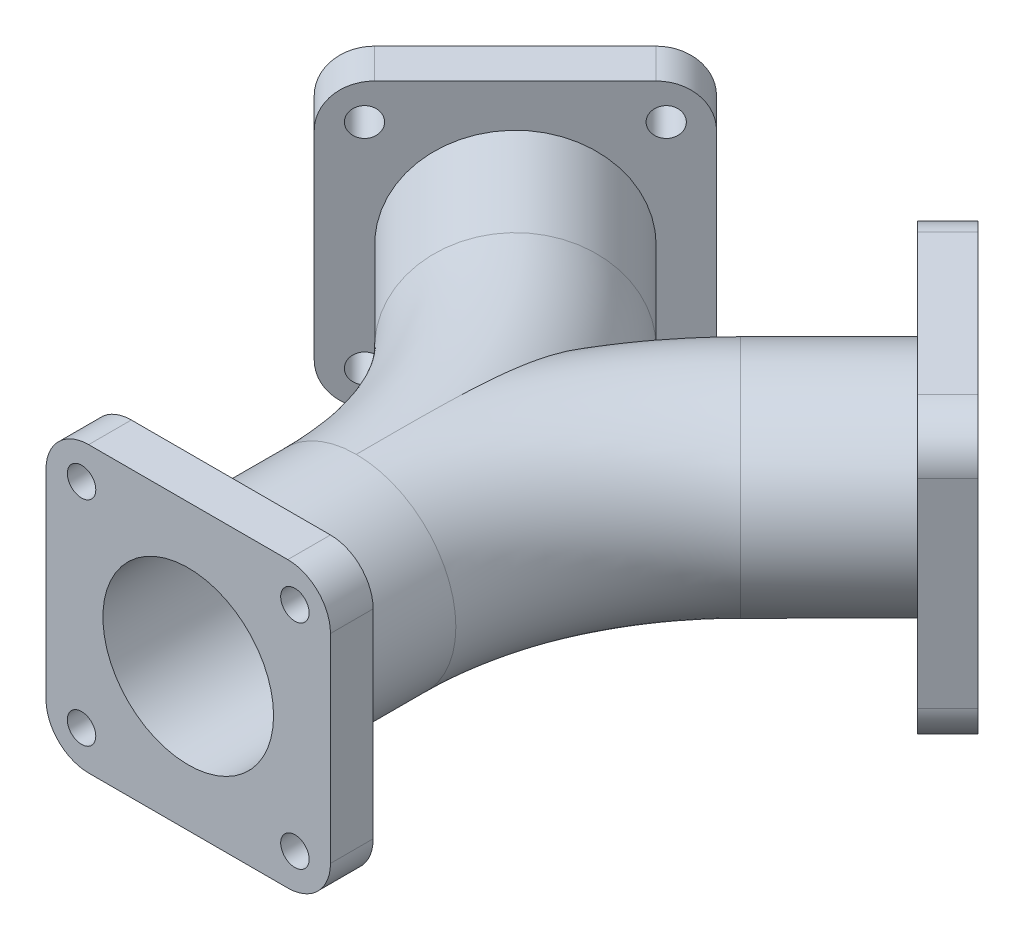
SolidWorks part; units mm, degrees
ref_plane "Alzado" through (0, 0, 0) normal (0, 0, 1) x (1, 0, 0)
ref_plane "Planta" through (0, 0, 0) normal (0, 1, 0) x (1, 0, 0)
ref_plane "Vista lateral" through (0, 0, 0) normal (1, 0, 0) x (0, 0, -1)
sketch "Croquis1" plane through (0, 0, 0) normal (0, 0, 1) x (1, 0, 0)
  line L1 (-50, -50) -> (50, -50)
  line L2 (-50, -50) -> (-50, 50)
  line L3 (-50, 50) -> (50, 50)
  line L4 (50, -50) -> (50, 50)
  line L5 (-50, -50) -> (50, 50) construction
  line L6 (-50, 50) -> (50, -50) construction
  point P0 (0, 0)
  dimension "D1" = 100
  dimension "D2" = 100
extrude "Saliente-Extruir1" add sketch "Croquis1" along normal blind 15
fillet "Redondeo1" radius 15 4 edges at (50, 50, 7.5) (-50, 50, 7.5) (-50, -50, 7.5) (50, -50, 7.5)
sketch "Croquis2" plane through (0, 0, 15) normal (0, 0, 1) x (1, 0, 0)
  circle A0 centre (0, 0) radius 30
  circle A2 centre (-37.5, -37.5) radius 5
  circle A3 centre (37.5, 37.5) radius 5
  circle A4 centre (37.5, -37.5) radius 5
  circle A5 centre (-37.5, 37.5) radius 5
extrude "Cortar-Extruir2" cut sketch "Croquis2" against normal blind 22
sketch "Croquis7" plane through (0, 0, 0) normal (0, 1, 0) x (1, 0, 0)
  line L0 (0, 0) -> (0, 44.0812)
  line L1 (39.5406, 139.5406) -> (70.7107, 170.7107)
  arc A0 (0, 44.0812) -> (39.5406, 139.5406) centre (135, 44.0812) cw
  dimension "D1" = 135
sketch "Croquis10" plane through (0, 0, 0) normal (0, 0, 1) x (1, 0, 0)
  circle A0 centre (0, 0) radius 30
  circle A1 centre (0, 0) radius 35
sweep "Barrer1" add profiles "Croquis10" path "Croquis7"
sketch "Croquis12" plane through (0, 0, 0) normal (0, 1, 0) x (1, 0, 0)
  line L0 (70.7107, 170.7107) -> (120.3144, 121.1069) construction
  line L1 (95.4594, 145.9619) -> (45.9619, 195.4594) construction
  line L2 (120.3144, 121.1069) -> (21.6981, 219.7232) construction
  line L3 (182.9938, 58.4276) -> (58.4276, 182.9938) construction
ref_plane "Plano1" through (120.7107, 0, -120.7107) normal (0.7071, 0, -0.7071) x (-0.7071, 0, -0.7071)
sketch "Croquis14" plane through (120.7107, 0, -120.7107) normal (0.7071, 0, -0.7071) x (-0.7071, 0, -0.7071)
  line L1 (20.7107, 50) -> (120.7107, 50)
  line L2 (20.7107, 50) -> (20.7107, -50)
  line L3 (20.7107, -50) -> (120.7107, -50)
  line L4 (120.7107, 50) -> (120.7107, -50)
  line L5 (20.7107, 50) -> (120.7107, -50) construction
  line L6 (20.7107, -50) -> (120.7107, 50) construction
  point P0 (70.7107, 0)
  dimension "D1" = 100
  dimension "D2" = 100
extrude "Saliente-Extruir2" add sketch "Croquis14" along normal blind 15
sketch "Croquis15" plane through (120.7107, 0, -120.7107) normal (0.7071, 0, -0.7071) x (-0.7071, 0, -0.7071)
  circle A0 centre (70.7107, 0) radius 30
  circle A1 centre (108.2107, -37.5) radius 5
  circle A2 centre (33.2107, -37.5) radius 5
  circle A3 centre (33.2107, 37.5) radius 5
  circle A4 centre (108.2107, 37.5) radius 5
extrude "Cortar-Extruir3" cut sketch "Croquis15" along normal blind 27
fillet "Redondeo2" radius 15 4 edges at (111.3693, 50, -140.6586) (111.3693, -50, -140.6586) (40.6586, 50, -211.3693) (40.6586, -50, -211.3693)
sketch "Croquis18" plane through (0, 0, 0) normal (0, 1, 0) x (1, 0, 0)
  line L0 (0, 0) -> (0, 44.0812)
  line L1 (35, 0) -> (-35, 0) construction
  line L2 (-39.5406, 139.5406) -> (-70.7107, 170.7107)
  arc A0 (0, 44.0812) -> (-39.5406, 139.5406) centre (-135, 44.0812) ccw
  dimension "D1" = 135
sketch "Croquis19" plane through (0, 0, 0) normal (0, 0, 1) x (1, 0, 0)
  circle A0 centre (0, 0) radius 30
  circle A1 centre (0, 0) radius 35
sweep "Barrer4" add profiles "Croquis19" path "Croquis18"
sketch "Croquis21" plane through (0, 0, 0) normal (0, 1, 0) x (1, 0, 0)
  line L0 (-70.7107, 170.7107) -> (-24.3051, 217.1162) construction
  line L1 (-49.4975, 191.9239) -> (-91.9239, 149.4975) construction
  line L2 (-24.3051, 217.1162) -> (-137.9274, 103.4939) construction
sketch "Croquis23" plane through (-120.7107, 0, -120.7107) normal (-0.7071, 0, -0.7071) x (-0.7071, 0, 0.7071)
  line L1 (-120.7107, -50) -> (-20.7107, -50)
  line L2 (-120.7107, -50) -> (-120.7107, 50)
  line L3 (-120.7107, 50) -> (-20.7107, 50)
  line L4 (-20.7107, -50) -> (-20.7107, 50)
  line L5 (-120.7107, -50) -> (-20.7107, 50) construction
  line L6 (-120.7107, 50) -> (-20.7107, -50) construction
  point P0 (-70.7107, 0)
  dimension "D1" = 100
extrude "Saliente-Extruir3" add sketch "Croquis23" along normal blind 15
sketch "Croquis24" plane through (-131.3173, 0, -131.3173) normal (-0.7071, 0, -0.7071) x (-0.7071, 0, 0.7071)
  line L0 (-70.7107, 0) -> (-136.3381, 0) construction
  line L1 (-136.3381, 0) -> (24.3481, 0) construction
  circle A0 centre (-70.7107, 0) radius 30
  circle A1 centre (-108.2107, 37.5) radius 5
  circle A2 centre (-108.2107, -37.5) radius 5
  circle A3 centre (-33.2107, -37.5) radius 5
  circle A4 centre (-33.2107, 37.5) radius 5
extrude "Cortar-Extruir4" cut sketch "Croquis24" against normal blind 15
fillet "Redondeo3" radius 15 4 edges at (-40.6586, -50, -211.3693) (-111.3693, -50, -140.6586) (-111.3693, 50, -140.6586) (-40.6586, 50, -211.3693)
sketch "Croquis28" plane through (120.7107, 0, -120.7107) normal (-0.7071, 0, 0.7071) x (0.7071, 0, 0.7071)
sweep "Cortar-Barrer1" cut path "Croquis18<4>" circular profile diameter 60 parameters "D3"=60
sketch "Croquis18<4>" plane through (0, 0, 0) normal (0, 1, 0) x (1, 0, 0) same geometry as "Croquis18"
sweep "Cortar-Barrer2" cut path "Croquis7<2>" circular profile diameter 60 parameters "D3"=60
sketch "Croquis7<2>" plane through (0, 0, 0) normal (0, 1, 0) x (1, 0, 0) same geometry as "Croquis7"
